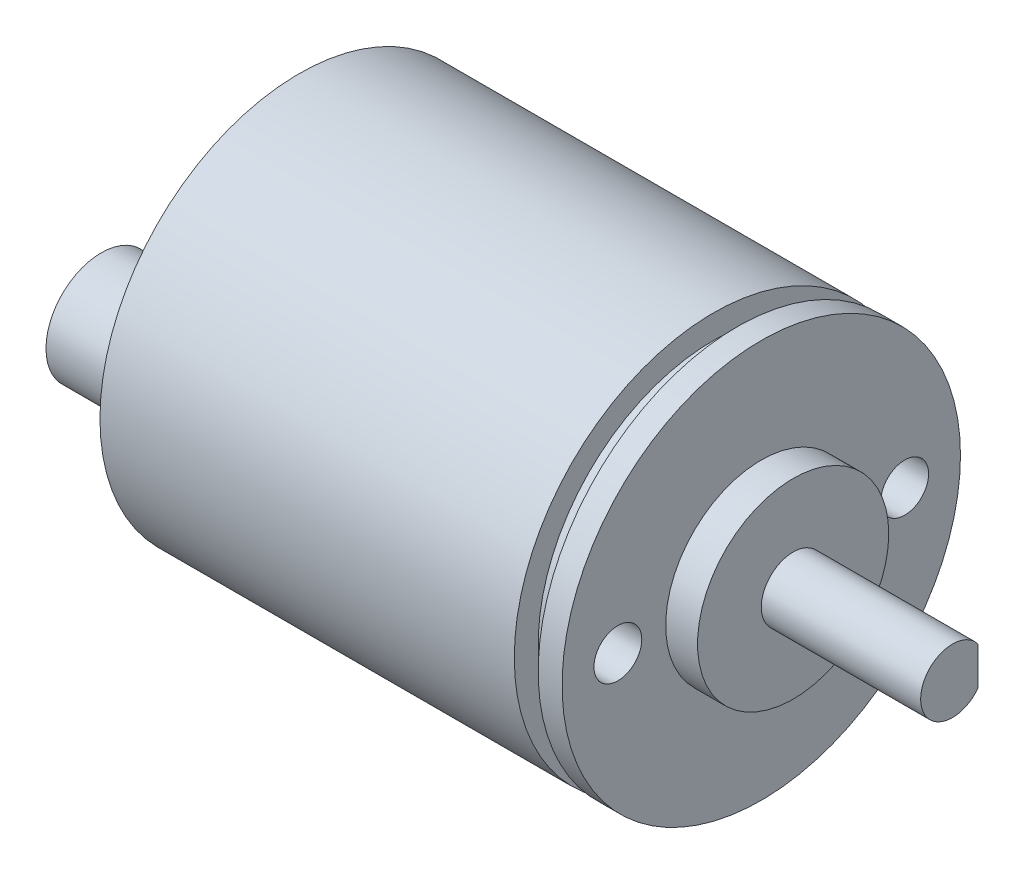
SolidWorks part; units mm, degrees
ref_plane "Front Plane" through (0, 0, 0) normal (0, 0, 1) x (1, 0, 0)
ref_plane "Top Plane" through (0, 0, 0) normal (0, 1, 0) x (1, 0, 0)
ref_plane "Right Plane" through (0, 0, 0) normal (1, 0, 0) x (0, 0, -1)
sketch "Sketch1" plane through (0, 0, 0) normal (1, 0, 0) x (0, 0, -1)
  circle A0 centre (0, 0) radius 12.5
  dimension "D1" = 25
extrude "Boss-Extrude1" add sketch "Sketch1" along normal blind 26
sketch "Sketch2" plane through (26, 0, 0) normal (1, 0, 0) x (0, 0, -1)
  circle A0 centre (0, 0) radius 11
  dimension "D1" = 22
extrude "Boss-Extrude2" add sketch "Sketch2" along normal blind 1.5
sketch "Sketch3" plane through (27.5, 0, 0) normal (1, 0, 0) x (0, 0, -1)
  circle A0 centre (0, 0) radius 12.5
  dimension "D1" = 25
extrude "Boss-Extrude3" add sketch "Sketch3" along normal blind 1.5
sketch "Sketch4" plane through (29, 0, 0) normal (1, 0, 0) x (0, 0, -1)
  circle A0 centre (0, 0) radius 6
  dimension "D1" = 12
extrude "Boss-Extrude4" add sketch "Sketch4" along normal blind 2
sketch "Sketch5" plane through (31, 0, 0) normal (1, 0, 0) x (0, 0, -1)
  circle A0 centre (0, 0) radius 2
  dimension "D1" = 4
extrude "Boss-Extrude5" add sketch "Sketch5" along normal blind 10
sketch "Sketch6" plane through (41, 0, 0) normal (1, 0, 0) x (0, 0, -1)
  line L1 (1.6, 3.2717) -> (4.2374, 3.2717)
  line L2 (1.6, 3.2717) -> (1.6, -3.3926)
  line L3 (1.6, -3.3926) -> (4.2374, -3.3926)
  line L4 (4.2374, 3.2717) -> (4.2374, -3.3926)
  circle A0 centre (0, 0) radius 2 construction
  dimension "D1" = 1.6
extrude "Cut-Extrude1" cut sketch "Sketch6" against normal blind 8
sketch "Sketch8" plane through (29, 0, 0) normal (1, 0, 0) x (0, 0, -1)
  circle A0 centre (9, 0) radius 1.5
  circle A1 centre (0, 0) radius 6 construction
  circle A2 centre (-9, 0) radius 1.5
  dimension "D1" = 3
  dimension "D2" = 9
  dimension "D3" = 2
extrude "Cut-Extrude2" cut sketch "Sketch8" against normal blind 6.35
sketch "Sketch9" plane through (0, 0, 0) normal (-1, 0, 0) x (0, 0, 1)
  circle A0 centre (6.9146, 0) radius 3.4714
extrude "Boss-Extrude6" add sketch "Sketch9" along normal blind 5.5
